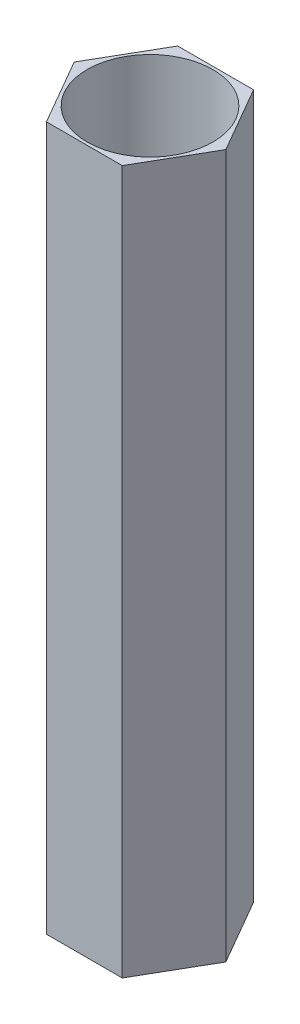
SolidWorks part; units mm, degrees
ref_plane "Front Plane" through (0, 0, 0) normal (0, 0, 1) x (1, 0, 0)
ref_plane "Top Plane" through (0, 0, 0) normal (0, 1, 0) x (1, 0, 0)
ref_plane "Right Plane" through (0, 0, 0) normal (1, 0, 0) x (0, 0, -1)
sketch "Sketch1" plane through (0, 0, 0) normal (0, 1, 0) x (1, 0, 0)
  line L1 (1.3568, -2.35) -> (2.7135, 0)
  line L2 (2.7135, 0) -> (1.3568, 2.35)
  line L3 (1.3568, 2.35) -> (-1.3568, 2.35)
  line L4 (-1.3568, 2.35) -> (-2.7135, 0)
  line L5 (-2.7135, 0) -> (-1.3568, -2.35)
  line L6 (-1.3568, -2.35) -> (1.3568, -2.35)
  circle A0 centre (0, 0) radius 2.35 construction
  circle A1 centre (0, 0) radius 2.25
  dimension "D1" = 4.5
  dimension "D2" = 4.7
extrude "Boss-Extrude1" add sketch "Sketch1" along normal blind 25.18
